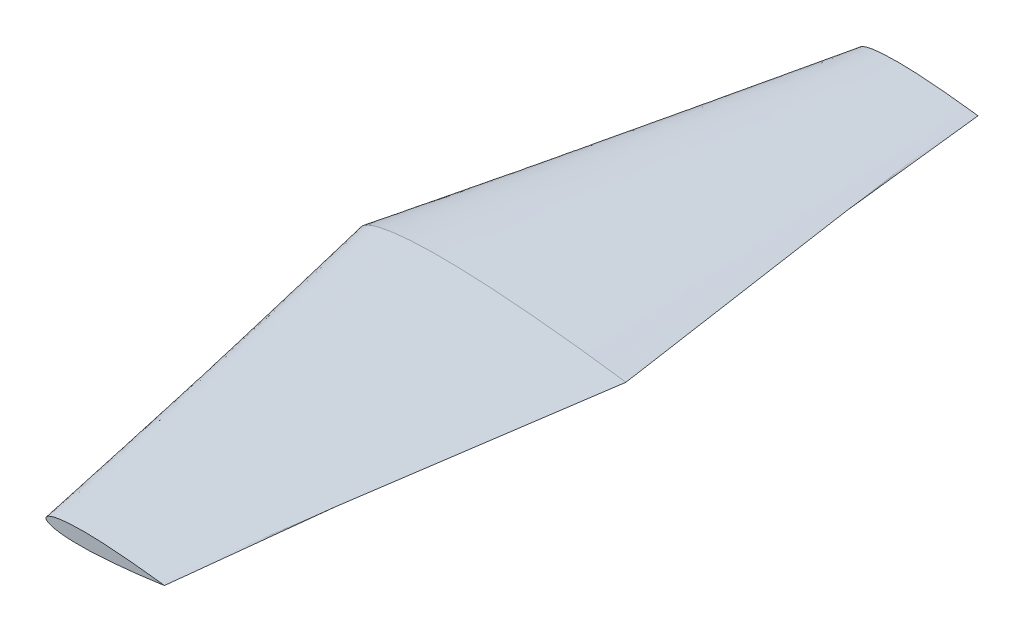
SolidWorks part; units mm, degrees
ref_plane "Front Plane" through (0, 0, 0) normal (0, 0, 1) x (1, 0, 0)
ref_plane "Top Plane" through (0, 0, 0) normal (0, 1, 0) x (1, 0, 0)
ref_plane "Right Plane" through (0, 0, 0) normal (1, 0, 0) x (0, 0, -1)
curve "Curve1"
  spline degree 3 poles (99.7885, -0.0238, 0) (100.0529, 0, 0) (99.7885, 0.0238, 0) (99.5705, 0.0667, 0) (99.036, 0.1373, 0) (98.371, 0.2353, 0) (97.4884, 0.3591, 0) (96.4285, 0.5079, 0) (95.1818, 0.6796, 0) (93.758, 0.8726, 0) (92.1611, 1.085, 0) (90.398, 1.3148, 0) (88.4753, 1.5596, 0) (86.4009, 1.8176, 0) (84.1828, 2.0861, 0) (81.8298, 2.3631, 0) (79.3511, 2.6463, 0) (76.7566, 2.9333, 0) (74.0566, 3.2219, 0) (71.2615, 3.5095, 0) (68.3826, 3.794, 0) (65.4311, 4.0727, 0) (62.4188, 4.3433, 0) (59.3574, 4.6029, 0) (56.2591, 4.8491, 0) (53.1361, 5.0789, 0) (50.0007, 5.2899, 0) (46.8653, 5.4786, 0) (43.7422, 5.643, 0) (40.6438, 5.7797, 0) (37.5823, 5.8866, 0) (34.5698, 5.9609, 0) (31.6181, 6.0005, 0) (28.7389, 6.0037, 0) (25.9436, 5.9689, 0) (23.2431, 5.8948, 0) (20.6482, 5.7809, 0) (18.1689, 5.627, 0) (15.8153, 5.4332, 0) (13.5963, 5.2006, 0) (11.5209, 4.9303, 0) (9.597, 4.6237, 0) (7.8323, 4.2831, 0) (6.2333, 3.9107, 0) (4.8064, 3.5089, 0) (3.5565, 3.0804, 0) (2.4879, 2.6273, 0) (1.6034, 2.152, 0) (0.9049, 1.6547, 0) (0.3931, 1.1335, 0) (0.0732, 0.5806, 0) (-0.035, 0, 0) (0.0732, -0.5806, 0) (0.3931, -1.1335, 0) (0.9049, -1.6547, 0) (1.6034, -2.152, 0) (2.4879, -2.6273, 0) (3.5565, -3.0804, 0) (4.8064, -3.5089, 0) (6.2333, -3.9107, 0) (7.8323, -4.2831, 0) (9.597, -4.6237, 0) (11.5209, -4.9303, 0) (13.5963, -5.2006, 0) (15.8153, -5.4332, 0) (18.1689, -5.627, 0) (20.6482, -5.7809, 0) (23.2431, -5.8948, 0) (25.9436, -5.9689, 0) (28.7389, -6.0037, 0) (31.6181, -6.0005, 0) (34.5698, -5.9609, 0) (37.5823, -5.8866, 0) (40.6438, -5.7797, 0) (43.7422, -5.643, 0) (46.8653, -5.4786, 0) (50.0007, -5.2899, 0) (53.1361, -5.0789, 0) (56.2591, -4.8491, 0) (59.3574, -4.6029, 0) (62.4188, -4.3433, 0) (65.4311, -4.0727, 0) (68.3826, -3.794, 0) (71.2615, -3.5095, 0) (74.0566, -3.2219, 0) (76.7566, -2.9333, 0) (79.3511, -2.6463, 0) (81.8298, -2.3631, 0) (84.1828, -2.0861, 0) (86.4009, -1.8176, 0) (88.4753, -1.5596, 0) (90.398, -1.3148, 0) (92.1611, -1.085, 0) (93.758, -0.8726, 0) (95.1818, -0.6796, 0) (96.4285, -0.5079, 0) (97.4884, -0.3591, 0) (98.371, -0.2353, 0) (99.036, -0.1373, 0) (99.5705, -0.0667, 0) (99.7885, -0.0238, 0) (100.0529, 0, 0) (99.7885, 0.0238, 0) knots -0.004388 -0.001954 -0.000489 0 0.000489 0.001954 0.004388 0.007782 0.012122 0.01739 0.023565 0.030621 0.038531 0.047262 0.056777 0.067042 0.078012 0.089646 0.101895 0.114712 0.128044 0.14184 0.156045 0.170601 0.185451 0.200536 0.215796 0.231172 0.246601 0.262023 0.277378 0.292606 0.307646 0.322441 0.336934 0.35107 0.364794 0.378056 0.390808 0.403002 0.414595 0.425546 0.435819 0.44538 0.4542 0.462253 0.469523 0.475998 0.481678 0.486579 0.490741 0.494247 0.49725 0.5 0.50275 0.505753 0.509259 0.513421 0.518322 0.524002 0.530477 0.537747 0.5458 0.55462 0.564181 0.574454 0.585405 0.596998 0.609192 0.621944 0.635206 0.64893 0.663066 0.677559 0.692354 0.707394 0.722622 0.737977 0.753399 0.768828 0.784204 0.799464 0.814549 0.829399 0.843955 0.85816 0.871956 0.885288 0.898105 0.910354 0.921988 0.932958 0.943223 0.952738 0.961469 0.969379 0.976435 0.98261 0.987878 0.992218 0.995612 0.998046 0.999511 1 1.000489 1.001954 1.004388 periodic
sketch "Sketch4" plane through (0, 0, 0) normal (0, 0, 1) x (1, 0, 0)
  line L0 (0, 0) -> (150, 0) construction
  spline S1 degree 3 poles (149.6828, -0.0357) (150.0794, 0) (149.6828, 0.0357) (149.3558, 0.1001) (148.554, 0.206) (147.5565, 0.3529) (146.2326, 0.5387) (144.6428, 0.7618) (142.7727, 1.0195) (140.637, 1.309) (138.2417, 1.6275) (135.597, 1.9723) (132.713, 2.3394) (129.6014, 2.7264) (126.2742, 3.1291) (122.7447, 3.5446) (119.0267, 3.9695) (115.135, 4.4) (111.0848, 4.8328) (106.8923, 5.2642) (102.5739, 5.691) (98.1467, 6.109) (93.6282, 6.515) (89.0362, 6.9043) (84.3887, 7.2737) (79.7041, 7.6184) (75.0011, 7.9348) (70.2979, 8.2178) (65.6133, 8.4645) (60.9657, 8.6696) (56.3735, 8.8299) (51.8547, 8.9414) (47.4272, 9.0008) (43.1084, 9.0055) (38.9154, 8.9534) (34.8647, 8.8422) (30.9723, 8.6713) (27.2534, 8.4405) (23.7229, 8.1498) (20.3945, 7.8008) (17.2813, 7.3954) (14.3955, 6.9356) (11.7484, 6.4246) (9.35, 5.8661) (7.2096, 5.2634) (5.3347, 4.6205) (3.7319, 3.9409) (2.4051, 3.2281) (1.3573, 2.4821) (0.5896, 1.7002) (0.1098, 0.8709) (-0.0525, 0) (0.1098, -0.8709) (0.5896, -1.7002) (1.3573, -2.4821) (2.4051, -3.2281) (3.7319, -3.9409) (5.3347, -4.6205) (7.2096, -5.2634) (9.35, -5.8661) (11.7484, -6.4246) (14.3955, -6.9356) (17.2813, -7.3954) (20.3945, -7.8008) (23.7229, -8.1498) (27.2534, -8.4405) (30.9723, -8.6713) (34.8647, -8.8422) (38.9154, -8.9534) (43.1084, -9.0055) (47.4272, -9.0008) (51.8547, -8.9414) (56.3735, -8.8299) (60.9657, -8.6696) (65.6133, -8.4645) (70.2979, -8.2178) (75.0011, -7.9348) (79.7041, -7.6184) (84.3887, -7.2737) (89.0362, -6.9043) (93.6282, -6.515) (98.1467, -6.109) (102.5739, -5.691) (106.8923, -5.2642) (111.0848, -4.8328) (115.135, -4.4) (119.0267, -3.9695) (122.7447, -3.5446) (126.2742, -3.1291) (129.6014, -2.7264) (132.713, -2.3394) (135.597, -1.9723) (138.2417, -1.6275) (140.637, -1.309) (142.7727, -1.0195) (144.6428, -0.7618) (146.2326, -0.5387) (147.5565, -0.3529) (148.554, -0.206) (149.3558, -0.1001) (149.6828, -0.0357) (150.0794, 0) (149.6828, 0.0357) knots -0.004388 -0.001954 -0.000489 0 0.000489 0.001954 0.004388 0.007782 0.012122 0.01739 0.023565 0.030621 0.038531 0.047262 0.056777 0.067042 0.078012 0.089646 0.101895 0.114712 0.128044 0.14184 0.156045 0.170601 0.185451 0.200536 0.215796 0.231172 0.246601 0.262023 0.277378 0.292606 0.307646 0.322441 0.336934 0.35107 0.364794 0.378056 0.390808 0.403002 0.414595 0.425546 0.435819 0.44538 0.4542 0.462253 0.469523 0.475998 0.481678 0.486579 0.490741 0.494247 0.49725 0.5 0.50275 0.505753 0.509259 0.513421 0.518322 0.524002 0.530477 0.537747 0.5458 0.55462 0.564181 0.574454 0.585405 0.596998 0.609192 0.621944 0.635206 0.64893 0.663066 0.677559 0.692354 0.707394 0.722622 0.737977 0.753399 0.768828 0.784204 0.799464 0.814549 0.829399 0.843955 0.85816 0.871956 0.885288 0.898105 0.910354 0.921988 0.932958 0.943223 0.952738 0.961469 0.969379 0.976435 0.98261 0.987878 0.992218 0.995612 0.998046 0.999511 1 1.000489 1.001954 1.004388 only from (150, 0) to (150, 0)
  point P1 (90, 0)
  dimension "D1" = 150
  dimension "D2" = 90
ref_plane "Plane1" through (0, 0, 230) normal (0, 0, 1) x (1, 0, 0)
sketch "Sketch5" plane through (0, 0, 230) normal (0, 0, 1) x (1, 0, 0)
  line L0 (159.1867, 0) -> (0, 0) construction
  spline S0 degree 3 poles (118.9169, -0.0169) (119.0939, 0.0002) (118.9167, 0.015) (118.7706, 0.0427) (118.4124, 0.0876) (117.9667, 0.1501) (117.3751, 0.229) (116.6648, 0.3238) (115.8293, 0.4331) (114.8751, 0.5559) (113.8049, 0.6908) (112.6234, 0.8367) (111.3349, 0.9919) (109.9448, 1.1552) (108.4584, 1.3248) (106.8817, 1.4996) (105.2208, 1.678) (103.4824, 1.8583) (101.6732, 2.0393) (99.8005, 2.2191) (97.8716, 2.3966) (95.8941, 2.5697) (93.876, 2.7372) (91.825, 2.8971) (89.7494, 3.0479) (87.6573, 3.1875) (85.557, 3.3145) (83.4568, 3.4266) (81.365, 3.5225) (79.2898, 3.6) (77.2395, 3.6576) (75.2222, 3.6936) (73.2457, 3.7068) (71.3178, 3.6958) (69.4464, 3.6598) (67.6386, 3.5979) (65.9017, 3.5098) (64.2424, 3.3955) (62.6673, 3.255) (61.1827, 3.0892) (59.7943, 2.8988) (58.5075, 2.6848) (57.3275, 2.4487) (56.2586, 2.1921) (55.305, 1.9166) (54.4701, 1.6239) (53.7567, 1.3157) (53.1666, 0.9935) (52.7012, 0.6574) (52.3609, 0.306) (52.1492, -0.0656) (52.0794, -0.4549) (52.1545, -0.8431) (52.3712, -1.2119) (52.7162, -1.5585) (53.1862, -1.8883) (53.7806, -2.2025) (54.4981, -2.501) (55.3369, -2.7823) (56.2942, -3.0448) (57.3665, -3.2868) (58.5496, -3.5069) (59.8391, -3.7034) (61.23, -3.875) (62.7167, -4.0206) (64.2935, -4.1397) (65.9542, -4.2314) (67.6922, -4.2959) (69.5007, -4.3333) (71.3724, -4.3438) (73.3002, -4.3286) (75.2764, -4.2887) (77.2931, -4.2252) (79.3424, -4.1398) (81.4163, -4.0341) (83.5067, -3.9098) (85.6052, -3.7692) (87.7035, -3.6137) (89.7935, -3.4457) (91.8669, -3.2667) (93.9155, -3.079) (95.9312, -2.8841) (97.9061, -2.6841) (99.8324, -2.4805) (101.7025, -2.2752) (103.509, -2.0697) (105.2449, -1.8658) (106.9032, -1.6648) (108.4774, -1.4687) (109.9614, -1.2788) (111.3491, -1.0967) (112.6353, -0.924) (113.8148, -0.7621) (114.883, -0.6127) (115.8355, -0.477) (116.6694, -0.3563) (117.3784, -0.2519) (117.9688, -0.1649) (118.4136, -0.0963) (118.7712, -0.0466) (118.9169, -0.0169) (119.0939, 0.0002) (118.9167, 0.015) knots -0.004388 -0.001954 -0.000489 0 0.000489 0.001954 0.004388 0.007782 0.012122 0.01739 0.023565 0.030621 0.038531 0.047262 0.056777 0.067042 0.078012 0.089646 0.101895 0.114712 0.128044 0.14184 0.156045 0.170601 0.185451 0.200536 0.215796 0.231172 0.246601 0.262023 0.277378 0.292606 0.307646 0.322441 0.336934 0.35107 0.364794 0.378056 0.390808 0.403002 0.414595 0.425546 0.435819 0.44538 0.4542 0.462253 0.469523 0.475998 0.481678 0.486579 0.490741 0.494247 0.49725 0.5 0.50275 0.505753 0.509259 0.513421 0.518322 0.524002 0.530477 0.537747 0.5458 0.55462 0.564181 0.574454 0.585405 0.596998 0.609192 0.621944 0.635206 0.64893 0.663066 0.677559 0.692354 0.707394 0.722622 0.737977 0.753399 0.768828 0.784204 0.799464 0.814549 0.829399 0.843955 0.85816 0.871956 0.885288 0.898105 0.910354 0.921988 0.932958 0.943223 0.952738 0.961469 0.969379 0.976435 0.98261 0.987878 0.992218 0.995612 0.998046 0.999511 1 1.000489 1.001954 1.004388 only from (119.0584, 0) to (119.0584, 0)
  point P4 (90, 0)
  dimension "D1" = 90
ref_plane "Plane2" through (90, 0, 0) normal (1, 0, 0) x (0, 0, -1)
sketch "Sketch6" plane through (90, 0, 0) normal (1, 0, 0) x (0, 0, -1)
  line L0 (0, 0) -> (-230, 0) construction
  point P3 (0, 0)
  point P4 (0, 0)
  point P5 (0, 0)
  point P6 (0, 0)
  dimension "D1" = 230
loft "Loft1" add profiles "Sketch4", "Sketch5" connector at (50.4293, 8.9576, 0) connector at (71.8958, 3.6975, 230)
sketch "Sketch8" plane through (0, 0, 0) normal (0, 1, 0) x (1, 0, 0)
  line L0 (52.1028, -230) -> (119.0584, -230) construction
  line L1 (119.0584, -230) -> (120.8452, -212.4378) construction
  line L4 (120.8452, -212.4378) -> (48.4215, -212.4378) construction
  line L5 (48.4215, -212.4378) -> (52.1028, -230) construction
  line L6 (52.1028, -230) -> (119.0584, -230)
  spline S1 degree 3 poles (0, 0) (0.8165, -3.4827) (2.7713, -11.8216) (5.532, -23.6038) (8.6277, -36.8224) (11.3367, -48.3976) (13.4451, -57.4131) (14.8447, -63.4011) (15.7487, -67.2698) (16.715, -71.407) (17.5957, -75.179) (18.6361, -79.6368) (19.47, -83.2117) (20.1412, -86.0906) (20.5301, -87.7588) (21.0046, -89.7948) (21.4625, -91.7603) (22.0214, -94.1599) (22.7541, -97.307) (23.494, -100.4875) (24.4146, -104.4467) (25.245, -108.0206) (26.3868, -112.9402) (27.2178, -116.5247) (28.2274, -120.8853) (29.0293, -124.353) (30.1232, -129.0921) (31.0347, -133.0491) (31.9129, -136.8717) (32.704, -140.3232) (33.3629, -143.207) (33.8766, -145.4616) (34.251, -147.1074) (34.5897, -148.5994) (34.9329, -150.1144) (35.2586, -151.5546) (35.5939, -153.041) (35.9191, -154.4863) (36.2263, -155.8536) (36.6608, -157.7941) (37.0933, -159.7335) (37.4875, -161.5081) (37.7449, -162.67) (38.095, -164.2537) (38.4201, -165.7291) (38.9186, -167.9986) (39.3122, -169.7969) (39.8371, -172.204) (40.2617, -174.1571) (40.8045, -176.6619) (41.469, -179.7383) (42.1553, -182.9295) (42.9022, -186.4133) (43.5669, -189.5219) (44.1879, -192.4346) (44.6881, -194.7854) (45.0006, -196.2554) (45.2995, -197.6632) (45.7717, -199.8889) (46.2346, -202.0743) (46.7247, -204.3921) (46.9547, -205.4808) (47.3345, -207.2794) (47.6652, -208.8471) (48.1689, -211.2375) (48.6056, -213.3122) (49.1187, -215.7528) (49.6064, -218.0749) (50.0226, -220.0591) (50.4145, -221.9289) (50.6415, -223.0126) (50.9271, -224.3765) (51.1274, -225.3335) (51.4406, -226.8312) (51.733, -228.2299) (51.9903, -229.4612) (52.0919, -229.9478) (52.1028, -230) knots 0 0 0 0 0.045503 0.108951 0.153936 0.218201 0.260173 0.271712 0.296424 0.310711 0.325755 0.345698 0.368939 0.372451 0.383301 0.390729 0.399044 0.408972 0.42207 0.440147 0.45051 0.473777 0.486819 0.514754 0.520582 0.543754 0.560029 0.582451 0.595407 0.60992 0.627495 0.633036 0.639335 0.648966 0.652498 0.659096 0.66775 0.671882 0.677942 0.685579 0.697181 0.703222 0.708706 0.712321 0.723856 0.727925 0.74188 0.747273 0.759266 0.767304 0.779875 0.799301 0.808825 0.825197 0.839738 0.84671 0.85577 0.858855 0.865016 0.884713 0.887272 0.895152 0.898868 0.910656 0.915533 0.929943 0.937628 0.947257 0.960128 0.963417 0.97156 0.974213 0.981145 0.983997 0.993677 0.999322 1 1 1 1 construction
  spline S2 degree 1 poles (52.1028, -230) (119.0584, -230) knots 0 0 1 1
  spline S3 degree 3 poles (52.1028, -230) (57.3759, -243.386) (84.8063, -257.5674) (116.9593, -249.0877) (119.0584, -230) knots 0 0 0 0 0.472921 1 1 1 1
  point P7 (73.663, -248.84)
  point P9 (94.3257, -251.0509)
  point P11 (110.3116, -246.119)
  point P14 (61.8436, -244.2483)
  point P15 (110.9069, -244.7585)
  point P16 (64.2245, -244.6735)
  point P17 (60.9933, -242.3776)
  point P18 (84.377, -251.7311)
  point P19 (108.1008, -247.2244)
  point P20 (0, 0)
  point P21 (108.7695, -248.6765)
  point P22 (107.6183, -248.2702)
mirror "Mirror2" about plane through (0, 0, 0) normal (0, 0, 1) of "Loft1"
